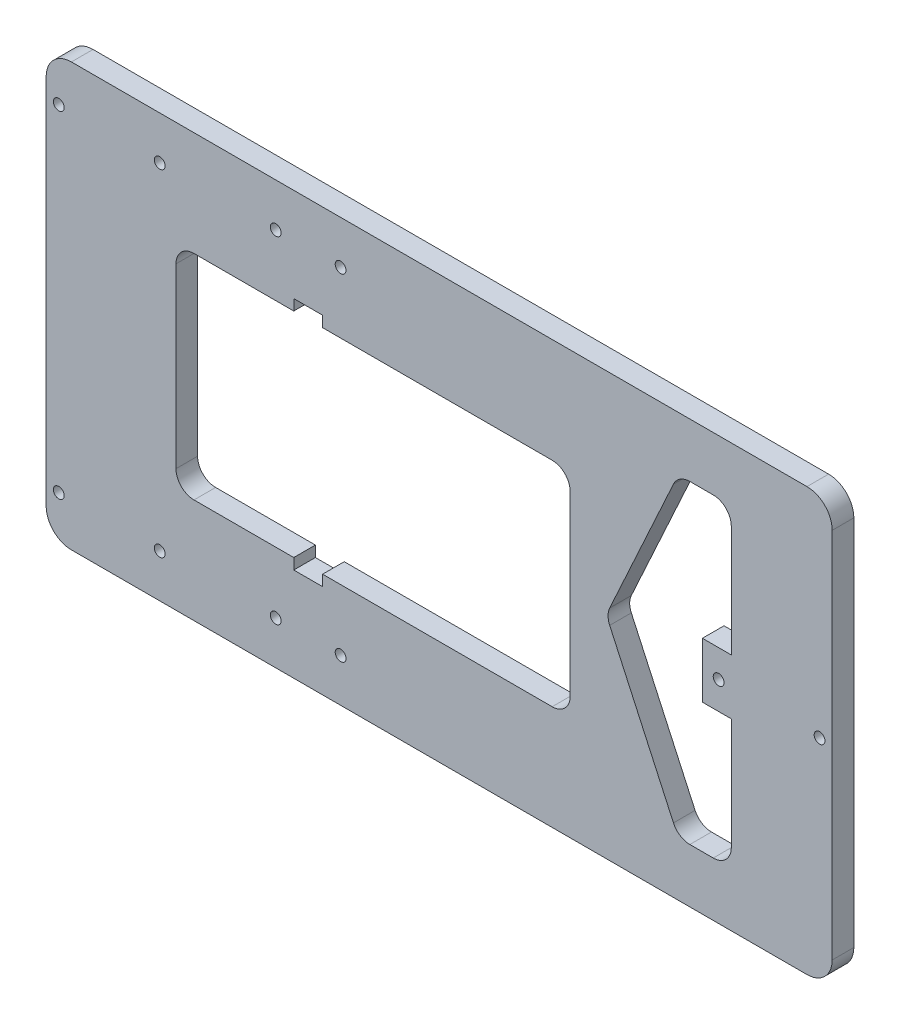
SolidWorks part; units mm, degrees
material "Beech"
ref_plane "Front Plane" through (0, 0, 0) normal (0, 0, 1) x (1, 0, 0)
ref_plane "Top Plane" through (0, 0, 0) normal (0, 1, 0) x (1, 0, 0)
ref_plane "Right Plane" through (0, 0, 0) normal (1, 0, 0) x (0, 0, -1)
sketch "Sketch1" plane through (0, 0, 0) normal (0, 0, 1) x (1, 0, 0)
  line L0 (-242.1092, 256.3436) -> (-242.1092, 139.1436) construction
  line L1 (-59.1092, 256.3436) -> (-59.1092, 139.1436) construction
  line L2 (-242.1092, 139.1436) -> (-59.1092, 139.1436) construction
  line L3 (-150.6092, 256.3436) -> (-150.6092, 306.7436) construction
  line L4 (-238.1092, 139.1436) -> (-246.1092, 139.1436) construction
  line L5 (-242.1092, 256.3436) -> (-59.1092, 256.3436) construction
  line L6 (-238.1092, 139.1436) -> (-238.1092, 256.3436) construction
  line L7 (-238.1092, 256.3436) -> (-246.1092, 256.3436) construction
  line L8 (-246.1092, 139.1436) -> (-246.1092, 256.3436) construction
  line L9 (-238.1092, 139.1436) -> (-246.1092, 256.3436) construction
  line L10 (-238.1092, 256.3436) -> (-246.1092, 139.1436) construction
  line L11 (-55.1092, 139.1436) -> (-63.1092, 139.1436) construction
  line L12 (-55.1092, 139.1436) -> (-55.1092, 256.3436) construction
  line L13 (-55.1092, 256.3436) -> (-63.1092, 256.3436) construction
  line L14 (-63.1092, 139.1436) -> (-63.1092, 256.3436) construction
  line L15 (-55.1092, 139.1436) -> (-63.1092, 256.3436) construction
  line L16 (-55.1092, 256.3436) -> (-63.1092, 139.1436) construction
  line L17 (-231.6092, 232.3436) -> (-252.6092, 232.3436)
  line L18 (-231.6092, 232.3436) -> (-231.6092, 256.3436)
  line L19 (-231.6092, 256.3436) -> (-252.6092, 256.3436)
  line L20 (-252.6092, 232.3436) -> (-252.6092, 256.3436)
  line L21 (-231.6092, 232.3436) -> (-252.6092, 256.3436) construction
  line L22 (-231.6092, 256.3436) -> (-252.6092, 232.3436) construction
  line L23 (-252.6092, 163.1436) -> (-231.6092, 163.1436)
  line L24 (-252.6092, 163.1436) -> (-252.6092, 139.1436)
  line L25 (-252.6092, 139.1436) -> (-231.6092, 139.1436)
  line L26 (-231.6092, 163.1436) -> (-231.6092, 139.1436)
  line L27 (-252.6092, 163.1436) -> (-231.6092, 139.1436) construction
  line L28 (-252.6092, 139.1436) -> (-231.6092, 163.1436) construction
  line L29 (-48.6092, 185.7436) -> (-69.6092, 185.7436) construction
  line L30 (-48.6092, 185.7436) -> (-48.6092, 209.7436) construction
  line L31 (-48.6092, 209.7436) -> (-69.6092, 209.7436) construction
  line L32 (-69.6092, 185.7436) -> (-69.6092, 209.7436) construction
  line L33 (-48.6092, 185.7436) -> (-69.6092, 209.7436) construction
  line L34 (-48.6092, 209.7436) -> (-69.6092, 185.7436) construction
  line L35 (-150.6092, 306.7436) -> (-259.6092, 306.7436) construction
  line L37 (-259.6092, 256.3436) -> (-41.6092, 256.3436)
  line L38 (-259.6092, 306.7436) -> (-41.6092, 306.7436)
  line L39 (-259.6092, 306.7436) -> (-259.6092, 88.7436)
  line L40 (-259.6092, 88.7436) -> (-41.6092, 88.7436)
  line L41 (-41.6092, 306.7436) -> (-41.6092, 88.7436)
  line L42 (-259.6092, 256.3436) -> (-259.6092, 139.1436)
  line L43 (-259.6092, 139.1436) -> (-41.6092, 139.1436)
  line L44 (-41.6092, 256.3436) -> (-41.6092, 139.1436)
  circle A0 centre (-269.6092, 244.3436) radius 2.5
  circle A1 centre (-31.6092, 197.7436) radius 2.5
  circle A3 centre (-269.6092, 151.1436) radius 2.5
  circle A6 centre (-256.1092, 244.3436) radius 1.5
  circle A7 centre (-256.1092, 151.1436) radius 1.5
  circle A8 centre (-45.1092, 197.7436) radius 1.5
  circle A9 centre (-73.1092, 197.7436) radius 1.5
  circle A10 centre (-228.1092, 244.3436) radius 1.5
  circle A11 centre (-228.1092, 151.1436) radius 1.5
  point P0 (-242.1092, 197.7436)
  point P9 (-59.1092, 197.7436)
  point P14 (-242.1092, 244.3436)
  point P19 (-242.1092, 151.1436)
  point P24 (-59.1092, 197.7436)
  point P34 (-150.6092, 197.7436)
  dimension "D11" = 5
  dimension "D12" = 10
  dimension "D15" = 3
  dimension "D20" = 5
  dimension "D21" = 10
  dimension "D22" = 5
  dimension "D23" = 3.5
  dimension "D24" = 3.5
  dimension "D1" = 183
  dimension "D2" = 8
  dimension "D3" = 8
  dimension "D4" = 21
  dimension "D5" = 24
  dimension "D6" = 117.2
  dimension "D7" = 21
  dimension "D8" = 24
  dimension "D9" = 21
  dimension "D10" = 24
  dimension "D16" = 109
  dimension "D17" = 109
  dimension "D18" = 218
  dimension "D19" = 218
extrude "Boss-Extrude1" add sketch "Sketch1" along normal blind 6 contours A6 | A10 | A11 | A8 | A9 | L37 L44 L43 L42 | A7 region at (-256.1092, 244.3436, 0) region at (-45.1092, 197.7436, 0) region at (-73.1092, 197.7436, 0) region at (-228.1092, 244.3436, 0) region at (-228.1092, 151.1436, 0)
sketch "Sketch2" plane through (0, 0, 6) normal (0, 0, 1) x (1, 0, 0)
  line L0 (-259.6092, 256.3436) -> (-41.6092, 256.3436) construction
  line L1 (-259.6092, 256.3436) -> (-41.6092, 256.3436)
  line L2 (-186.9425, 273.3122) -> (-186.9425, 128.0805) construction
  line L3 (-259.6092, 256.3436) -> (-259.6092, 139.1436) construction
  line L4 (-256.1092, 244.3436) -> (-152.9234, 244.3436) construction
  line L5 (-256.1092, 151.1436) -> (-151.5972, 151.1436) construction
  circle A0 centre (-195.9425, 151.1436) radius 1.5
  circle A1 centre (-177.9425, 151.1436) radius 1.5
  circle A3 centre (-195.9425, 244.3436) radius 1.5
  circle A4 centre (-177.9425, 244.3436) radius 1.5
  dimension "D2" = 3
  dimension "D3" = 9
  dimension "D4" = 9
  dimension "D5" = 9
  dimension "D6" = 9
  dimension "D1" = 72.6667
extrude "Cut-Extrude1" cut sketch "Sketch2" against normal blind 6 contours A3 | A4 | A1 | A0
fillet "Fillet1" radius 7 4 edges at (-41.6092, 139.1436, 3) (-41.6092, 256.3436, 3) (-259.6092, 139.1436, 3) (-259.6092, 256.3436, 3)
sketch "Sketch3" plane through (0, 0, 0) normal (0, 0, -1) x (-1, 0, 0)
  line L0 (223.6092, 227.3436) -> (223.6092, 168.1436)
  line L1 (223.6092, 227.3436) -> (114.2758, 227.3436)
  line L2 (114.2758, 227.3436) -> (114.2758, 168.1436)
  line L3 (114.2758, 168.1436) -> (223.6092, 168.1436)
  line L5 (231.6092, 232.3436) -> (235.6283, 232.3436) construction
  line L6 (249.6092, 163.1436) -> (234.6092, 163.1436) construction
  line L7 (41.6092, 249.3436) -> (41.6092, 146.1436) construction
  dimension "D1" = 5
  dimension "D2" = 5
  dimension "D3" = 72.6667
extrude "Cut-Extrude2" cut sketch "Sketch3" against normal blind 10
fillet "Fillet3" radius 5 4 edges at (-114.2758, 168.1436, 3) (-223.6092, 168.1436, 3) (-223.6092, 227.3436, 3) (-114.2758, 227.3436, 3)
sketch "Sketch4" plane through (0, 0, 0) normal (0, 0, -1) x (-1, 0, 0)
  line L0 (84.299, 241.3436) -> (69.5973, 241.3436)
  line L1 (69.5973, 205.4186) -> (69.5973, 241.3436)
  line L2 (69.5973, 205.4186) -> (77.6092, 205.4186)
  line L3 (77.6092, 205.4186) -> (77.6092, 190.0686)
  line L4 (77.6092, 190.0686) -> (69.5973, 190.0686)
  line L5 (69.5973, 190.0686) -> (69.5973, 154.1436)
  line L6 (69.5973, 154.1436) -> (84.299, 154.1436)
  line L7 (84.299, 154.1436) -> (104.2758, 197.7436)
  line L8 (104.2758, 197.7436) -> (84.299, 241.3436)
  line L9 (252.6092, 256.3436) -> (48.6092, 256.3436) construction
  line L10 (252.6092, 139.1436) -> (48.6092, 139.1436) construction
  line L11 (114.2758, 222.3436) -> (114.2758, 173.1436) construction
  dimension "D1" = 15
  dimension "D2" = 15
  dimension "D3" = 10
extrude "Cut-Extrude3" cut sketch "Sketch4" against normal blind 10
fillet "Fillet4" radius 5 5 edges at (-69.5973, 154.1436, 3) (-84.299, 154.1436, 3) (-104.2758, 197.7436, 3) (-84.299, 241.3436, 3) (-69.5973, 241.3436, 3)
sketch "Sketch5" plane through (0, 0, 0) normal (0, 0, -1) x (-1, 0, 0)
  line L0 (179.4425, 244.3436) -> (194.4425, 244.3436) construction
  line L1 (186.9425, 244.3436) -> (186.9425, 227.3436) construction
  line L2 (218.6092, 227.3436) -> (119.2758, 227.3436) construction
  line L4 (190.9425, 165.1436) -> (182.9425, 165.1436)
  line L5 (190.9425, 165.1436) -> (190.9425, 230.3436)
  line L6 (190.9425, 230.3436) -> (182.9425, 230.3436)
  line L7 (182.9425, 165.1436) -> (182.9425, 230.3436)
  line L8 (119.2758, 168.1436) -> (218.6092, 168.1436) construction
  circle A0 centre (177.9425, 244.3436) radius 1.5 construction
  circle A1 centre (195.9425, 244.3436) radius 1.5 construction
  dimension "D1" = 8
  dimension "D2" = 3
  dimension "D3" = 3
extrude "Cut-Extrude4" cut sketch "Sketch5" against normal blind 10
